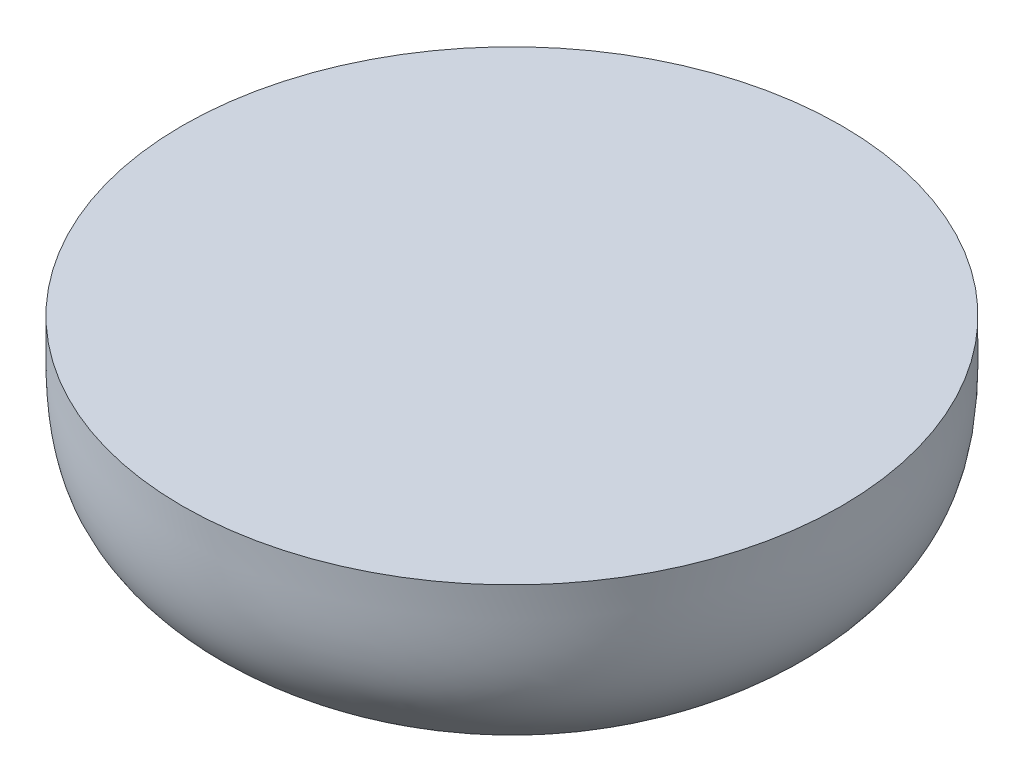
SolidWorks part; units mm, degrees
other "Camera1"
ref_plane "Front Plane" through (0, 0, 0) normal (0, 0, 1) x (1, 0, 0)
ref_plane "Top Plane" through (0, 0, 0) normal (0, 1, 0) x (1, 0, 0)
ref_plane "Right Plane" through (0, 0, 0) normal (1, 0, 0) x (0, 0, -1)
sketch "Sketch1" plane through (0, 0, 0) normal (0, 0, 1) x (1, 0, 0)
  line L0 (0, 45.2932) -> (0, -50.5102) construction
  line L1 (0, 18.1015) -> (51.8539, 18.1015)
  line L2 (0, -19.9985) -> (25.4, -19.9985)
  line L3 (0, -19.9985) -> (0, 18.1015)
  spline S0 degree 3 poles (51.8539, 18.1015) (51.7859, 12.2853) (53.2941, -6.5665) (32.6841, -14.6207) (25.4, -19.9985) knots 0 0 0 0 0.363726 1 1 1 1
  point P7 (40.021, -10.7455)
  point P8 (51.8539, 11.4616)
  point P9 (49.9568, 0)
  dimension "D1" = 25.4
revolve "Revolve1" add sketch "Sketch1" angle 360 about L0
sketch "Sketch2" plane through (0, -19.9985, 0) normal (0, -1, 0) x (1, 0, 0)
  circle A1 centre (0, 0) radius 18.6103
extrude "Cut-Extrude1" cut sketch "Sketch2" against normal blind 2.54
fillet "Fillet1" radius 2.54 1 edges at (0, -19.9985, -18.6103)
